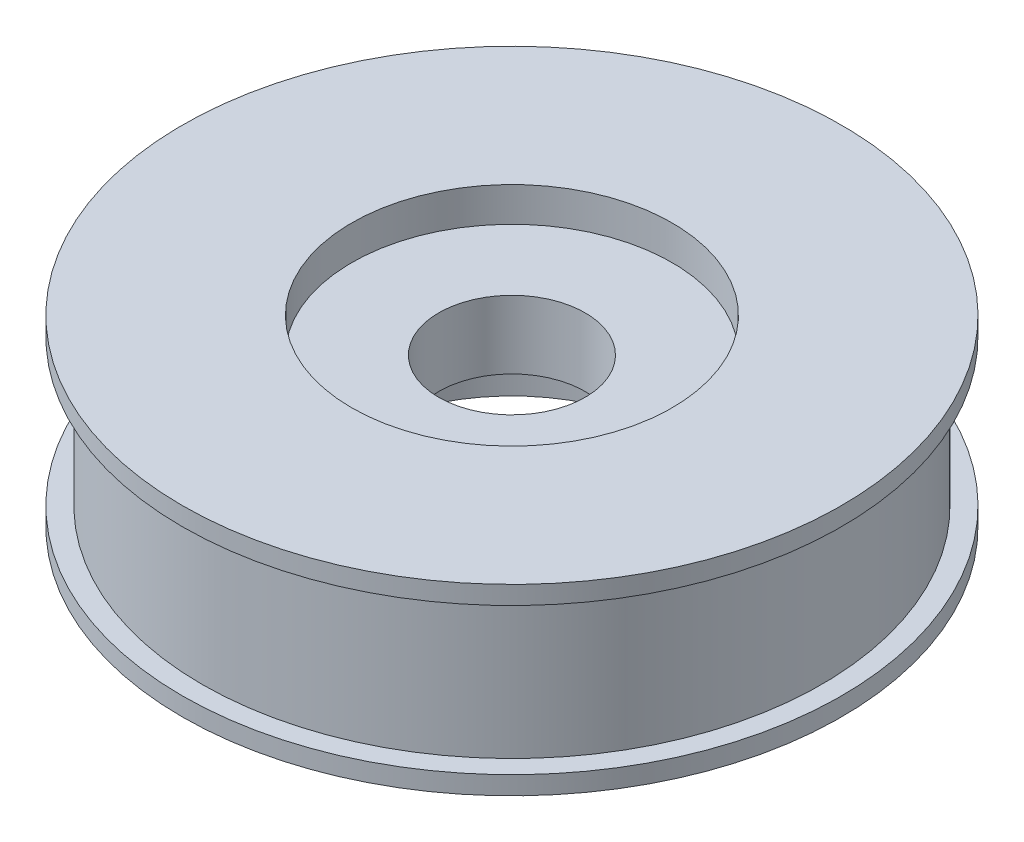
SolidWorks part; units mm, degrees
ref_plane "Front Plane" through (0, 0, 0) normal (0, 0, 1) x (1, 0, 0)
ref_plane "Top Plane" through (0, 0, 0) normal (0, 1, 0) x (1, 0, 0)
ref_plane "Right Plane" through (0, 0, 0) normal (1, 0, 0) x (0, 0, -1)
sketch "Sketch1" plane through (0, 0, 0) normal (0, 1, 0) x (1, 0, 0)
  circle A0 centre (0, 0) radius 22.86
  circle A1 centre (0, 0) radius 11.1125
  dimension "D1" = 45.72
  dimension "D2" = 22.225
extrude "Boss-Extrude1" add sketch "Sketch1" along normal mid plane 12.7
sketch "Sketch3" plane through (0, 0, 0) normal (0, 1, 0) x (1, 0, 0)
  circle A0 centre (0, 0) radius 21.4884
  circle A1 centre (0, 0) radius 22.86
  circle A2 centre (0, 0) radius 22.86 construction
  dimension "D1" = 42.9768
extrude "Cut-Extrude1" cut sketch "Sketch3" along normal offset from surface 1.27 and the other way offset from surface 1.27 contours A1 A0 region at (-22.2134, 0, 0) up to face at (0, 6.35, 22.86) other way up to face at (0, -6.35, 22.86)
sketch "Sketch4" plane through (0, 0, 0) normal (0, 1, 0) x (1, 0, 0)
  circle A0 centre (0, 0) radius 11.1125
  circle A1 centre (0, 0) radius 5.08
  circle A2 centre (0, 0) radius 11.1125 construction
  dimension "D1" = 10.16
extrude "Boss-Extrude5" add sketch "Sketch4" along normal offset from surface 2.3876 and the other way offset from surface 5.588 contours A0 A1 region at (-10.7982, 0, 0) up to face at (0, 6.35, 22.86) other way up to face at (0, -6.35, 22.86)
